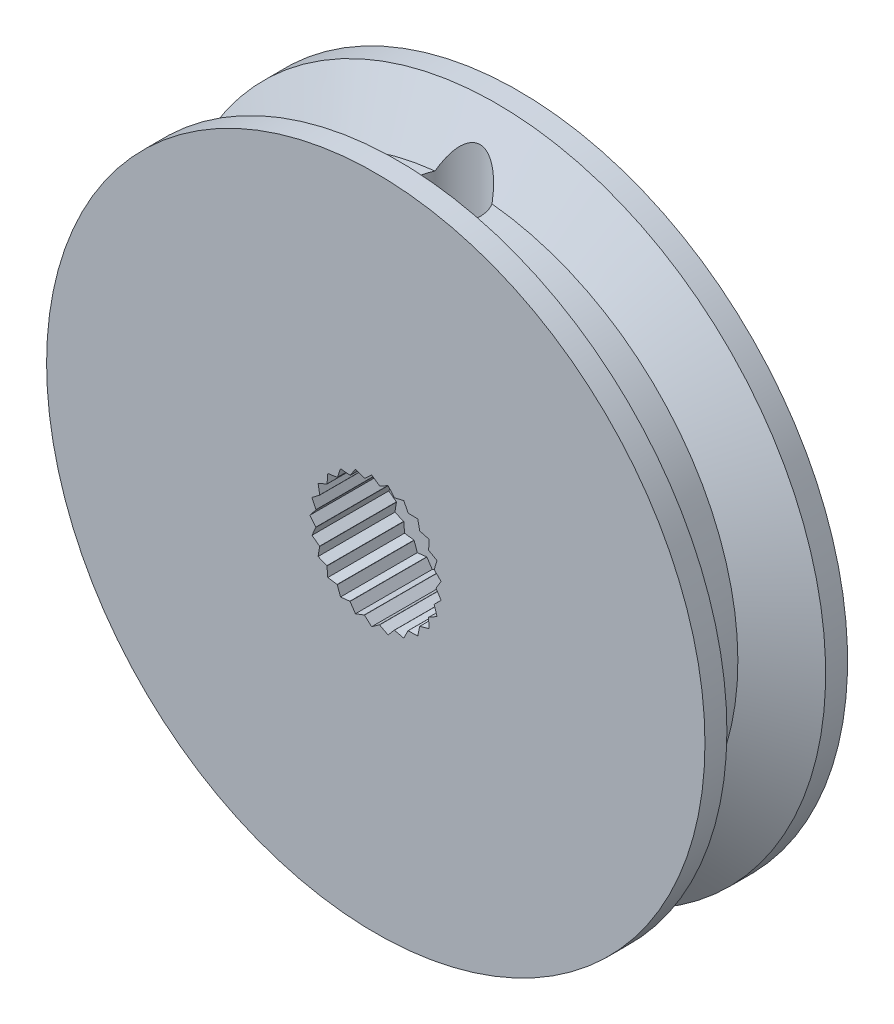
SolidWorks part; units mm, degrees
note: The reader was unsure of these and kept them because the rebuilt part matched: shared geometry of "Sketch1<2>".
ref_plane "Front Plane" through (0, 0, 0) normal (0, 0, 1) x (1, 0, 0)
ref_plane "Top Plane" through (0, 0, 0) normal (0, 1, 0) x (1, 0, 0)
ref_plane "Right Plane" through (0, 0, 0) normal (1, 0, 0) x (0, 0, -1)
sketch "Sketch1" plane through (0, 0, 0) normal (0, 0, 1) x (1, 0, 0)
  circle A0 centre (0, 0) radius 15
  circle A6 centre (0, 0) radius 4.5
  dimension "D1" = 30
  dimension "D2" = 9
extrude "Boss-Extrude1" add sketch "Sketch1" along normal blind 1
extrude "Boss-Extrude2" add sketch "Sketch1<2>" against normal blind 4.5 from surface at 1 contours A6 starting at face at (15, 0, 1)
sketch "Sketch1<2>" plane through (0, 0, 0) normal (0, 0, 1) x (1, 0, 0) same geometry as "Sketch1"
sketch "Sketch2" plane through (0, 0, 0) normal (0, 0, -1) x (-1, 0, 0)
  circle A0 centre (0, 0) radius 1.5
extrude "Cut-Extrude1" cut sketch "Sketch2" along normal blind 4.5
sketch "Sketch3" plane through (0, 0, -3.5) normal (0, 0, -1) x (-1, 0, 0)
  circle A0 centre (0, 0) radius 2.75
extrude "Cut-Extrude2" cut sketch "Sketch3" along normal blind 3.5 from surface at -4.5 starting at face at (15, 0, 1)
sketch "Sketch4" plane through (0, 0, -3.5) normal (0, 0, -1) x (-1, 0, 0)
  line L0 (0, 0) -> (-3, 0)
  line L1 (0, 0) -> (-2.9763, 0.376)
  line L2 (0, 0) -> (-2.9083, 0.7359)
  line L3 (-2.75, 0) -> (-2.9763, 0.376)
  line L4 (-2.666, 0.6746) -> (-2.9763, 0.376)
  circle A0 centre (0, 0) radius 3
  circle A1 centre (0, 0) radius 2.75 construction
  circle A2 centre (0, 0) radius 2.75 construction
  circle A3 centre (0, 0) radius 2.75
  dimension "D1" = 7.2
  dimension "D2" = 14.2
extrude "Cut-Extrude3" cut sketch "Sketch4" along normal blind 3.5 from surface at -4.5
pattern_circular "CirPattern1" count 25 over 360 about axis through (0, 0, 0) along (0, 0, 1) of "Cut-Extrude3"
sketch "Sketch5" plane through (0, 0, 0) normal (0, 1, 0) x (1, 0, 0)
  line L0 (-15, 0) -> (-12.5, 1.5)
  line L1 (-12.5, 1.5) -> (-12.5, 3)
  line L2 (-12.5, 3) -> (-15, 4.5)
  line L3 (-15, 4.5) -> (-15, 5.5)
  line L4 (-15, 5.5) -> (-10, 5.5)
  line L5 (-10, 5.5) -> (-10, 0)
  line L6 (15, 0) -> (-15, 0) construction
  line L7 (-15, 0) -> (-15, -1) construction
  line L8 (-15, 0) -> (-10, 0)
  dimension "D1" = 1.5
  dimension "D2" = 1
  dimension "D3" = 1.5
  dimension "D4" = 1.5
  dimension "D5" = 5
  dimension "D6" = 2.5
revolve "Revolve1" add sketch "Sketch5" angle 360 about axis through (0, 0, -2.5) along (0, 0, 1)
sketch "Sketch6" plane through (0, 0, 0) normal (0, 1, 0) x (1, 0, 0)
  line L1 (0, 5.5) -> (0, -1) construction
  line L3 (-4.5, -1) -> (4.5, -1) construction
  line L4 (15, 5.5) -> (-15, 5.5) construction
  circle A0 centre (0, 2.25) radius 1.5
  point P4 (0, 5.5)
  point P9 (0, 0)
  point P10 (-2.1682, 2.277)
  dimension "D1" = 3
extrude "Cut-Extrude4" cut sketch "Sketch6" along normal through all from surface contours A0
